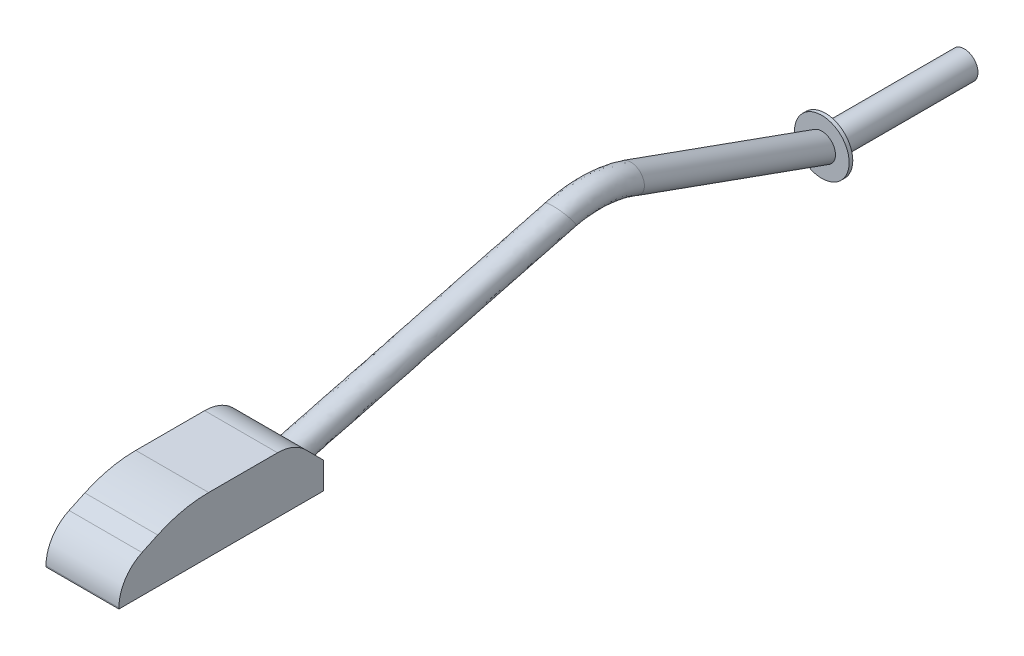
SolidWorks part; units mm, degrees
ref_plane "Alzado" through (0, 0, 0) normal (0, 0, 1) x (1, 0, 0)
ref_plane "Planta" through (0, 0, 0) normal (0, 1, 0) x (1, 0, 0)
ref_plane "Vista lateral" through (0, 0, 0) normal (1, 0, 0) x (0, 0, -1)
sketch "Croquis1" plane through (0, 0, 0) normal (0, 0, 1) x (1, 0, 0)
  circle A0 centre (0, 0) radius 75
  dimension "D1" = 150
extrude "Saliente-Extruir1" add sketch "Croquis1" along normal blind 10
sketch "Croquis2" plane through (0, 0, 10) normal (0, 0, 1) x (1, 0, 0)
  circle A0 centre (0, 0) radius 37.5
  dimension "D1" = 75
sketch3d "Croquis3D1"
  line L0 (0, 0, 0) -> (0, 192.0146, 534.1906)
  line L1 (0, 0, 0) -> (0, 0, 1500) construction
  line L2 (0, 200.8132, 728.9921) -> (0, 0, 1500)
  arc A0 (0, 192.0146, 534.1906) -> (0, 200.8132, 728.9921) centre (0, -118.5327, 645.8167) ccw
  point P6 (0, 828.6468, 2828.3425)
  point P7 (0, 3822.7298, 19840.2834)
  point P8 (0, 226.5361, 630.2308)
  point P9 (330, -118.5327, 645.8167)
  dimension "D1" = 1500
  dimension "D2" = 330
sweep "Barrer2" add profiles "Croquis2" path "Croquis3D1"
sketch "Croquis4" plane through (0, 0, 0) normal (0, 0, -1) x (-1, 0, 0)
  circle A0 centre (0, 0) radius 37.5
  dimension "D1" = 75
extrude "Saliente-Extruir3" add sketch "Croquis4" along normal blind 381
sketch "Croquis5" plane through (0, 0, 0) normal (1, 0, 0) x (0, 0, -1)
  line L0 (-1476.801, -33.9199) -> (-1476.801, 39.0137)
  line L1 (-748.1328, 228.7993) -> (-1519.1406, 27.986) construction
  line L2 (-1476.801, 39.0137) -> (-1525.4492, 87.6619)
  line L3 (-1603.2309, 119.8801) -> (-1792.1673, 119.8801)
  line L4 (-1931.9511, 88.8124) -> (-1975.042, 68.6627)
  line L5 (-2038.4474, -30.9814) -> (-2038.4474, -33.9199)
  line L6 (-2038.4474, -33.9199) -> (-1476.801, -33.9199)
  arc A0 (-1792.1673, 119.8801) -> (-1931.9511, 88.8124) centre (-1792.1673, -210.1199) ccw
  arc A1 (-1525.4492, 87.6619) -> (-1603.2309, 119.8801) centre (-1603.2309, 9.8801) ccw
  arc A2 (-1975.042, 68.6627) -> (-2038.4474, -30.9814) centre (-1928.4474, -30.9814) ccw
  dimension "D1" = 330
  dimension "D2" = 110
  dimension "D3" = 110
extrude "Saliente-Extruir4" add sketch "Croquis5" along normal blind 100 and the other way blind 100
sketch "Croquis6" plane through (0, -33.9199, 0) normal (0, -1, 0) x (1, 0, 0)
  line L1 (-70.684, 1524.1819) -> (70.684, 1524.1819)
  line L2 (-70.684, 1524.1819) -> (-70.684, 2005.099)
  line L3 (-70.684, 2005.099) -> (70.684, 2005.099)
  line L4 (70.684, 1524.1819) -> (70.684, 2005.099)
  line L5 (-70.684, 1524.1819) -> (70.684, 2005.099) construction
  line L6 (-70.684, 2005.099) -> (70.684, 1524.1819) construction
  point P0 (0, 1764.6405)
extrude "Cortar-Extruir1" cut sketch "Croquis6" against normal blind 20
